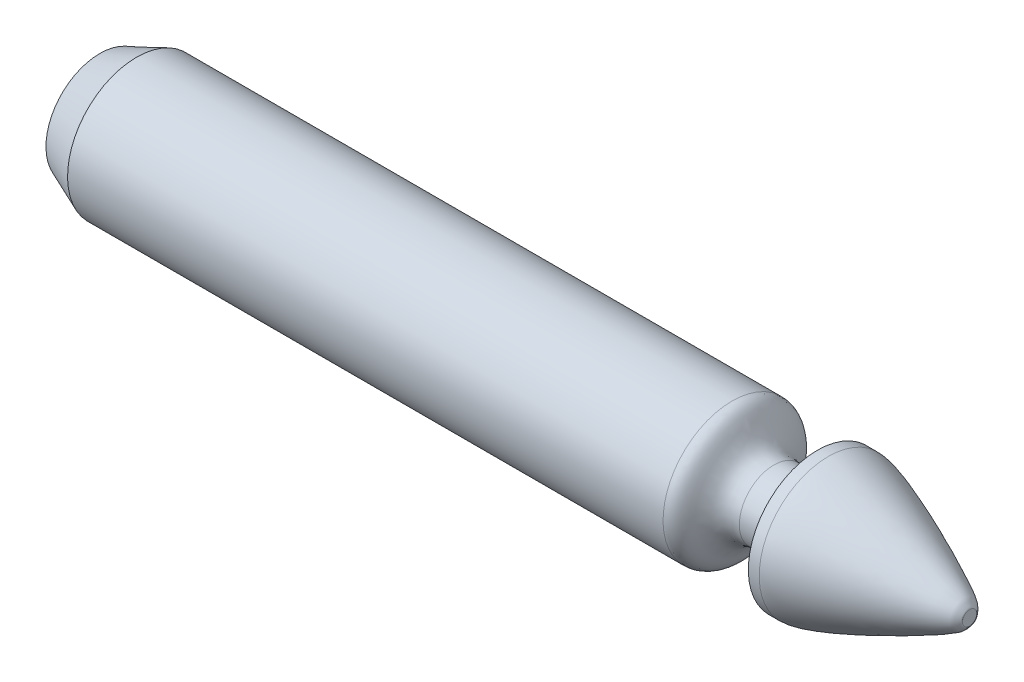
SolidWorks part; units mm, degrees
material "Stainless Steel (ferritic)"
ref_plane "Front" through (0, 0, 0) normal (0, 0, 1) x (1, 0, 0)
ref_plane "Top" through (0, 0, 0) normal (0, 1, 0) x (1, 0, 0)
ref_plane "Right" through (0, 0, 0) normal (1, 0, 0) x (0, 0, -1)
sketch "body_sketch" plane through (0, 0, 0) normal (0, 0, 1) x (1, 0, 0)
  line L4 (-6.5, 3.175) -> (-7, 3.175)
  line L5 (-10.9218, 3.175) -> (-38.31, 3.175)
  line L6 (-40, 0) -> (-40, 2.4778)
  line L7 (-40, 2.4778) -> (-38.31, 3.175)
  line L9 (-7, 3.175) -> (-7, 1.5875)
  line L10 (-7, 1.5875) -> (-9, 1.5875)
  line L13 (14.3233, 1.5875) -> (12.3233, 1.5875) construction
  line L14 (-10.9218, 3.175) -> (-7, 3.175) construction
  line L15 (0, 0) -> (-40, 0)
  line L17 (0, 0.3278) -> (0, 0)
  spline S0 degree 3 poles (-6.5, 3.175) (-5.4841, 3.175) (-0.4543, 0.8964) (-0.0546, 0.4243) (0, 0.3773) (0, 0.3278) knots 0 0 0 0 0.586138 0.686138 1 1 1 1
  spline S1 degree 3 poles (-10.9218, 3.175) (-10.0525, 3.175) (-10.25, 1.5875) (-9, 1.5875) knots 0 0 0 0 1 1 1 1
  point P2 (0, 0)
  point P3 (0, 0)
  point P4 (19.0685, 0.3583)
  point P5 (0, 0)
  point P8 (0, 0)
  point P11 (0.5136, 3.2252)
  point P12 (0.8329, 3.2668)
  point P15 (15.024, 3.175)
  point P16 (19.05, 0)
  point P17 (0, 0)
  point P18 (0, 0)
  point P22 (-0.2417, -0.3029)
  point P23 (0, 0)
  point P24 (0, 0)
  point P27 (0, 0)
  point P28 (0, 0)
  point P30 (-38.31, 3.175)
  point P31 (-10.9218, 3.175)
  point P32 (0, 0.3278)
  point P33 (-0.188, 0.5788)
  dimension "D1" = 3.175
  dimension "D2" = 0.5
  dimension "D3" = 2
  dimension "D4" = 1.5875
  dimension "D5" = 40
  dimension "D6" = 7
revolve "body" add sketch "body_sketch" angle 360 about L15
sketch "minimum_diameter" plane through (0, 0, 0) normal (1, 0, 0) x (0, 0, -1)
  circle A0 centre (0, 0) radius 1.5875 construction
  circle A2 centre (0, 0) radius 1.5875 construction
  point P5 (0, 0)
  point P6 (0, 0)
  point P8 (0, 0)
  point P9 (0, 0)
